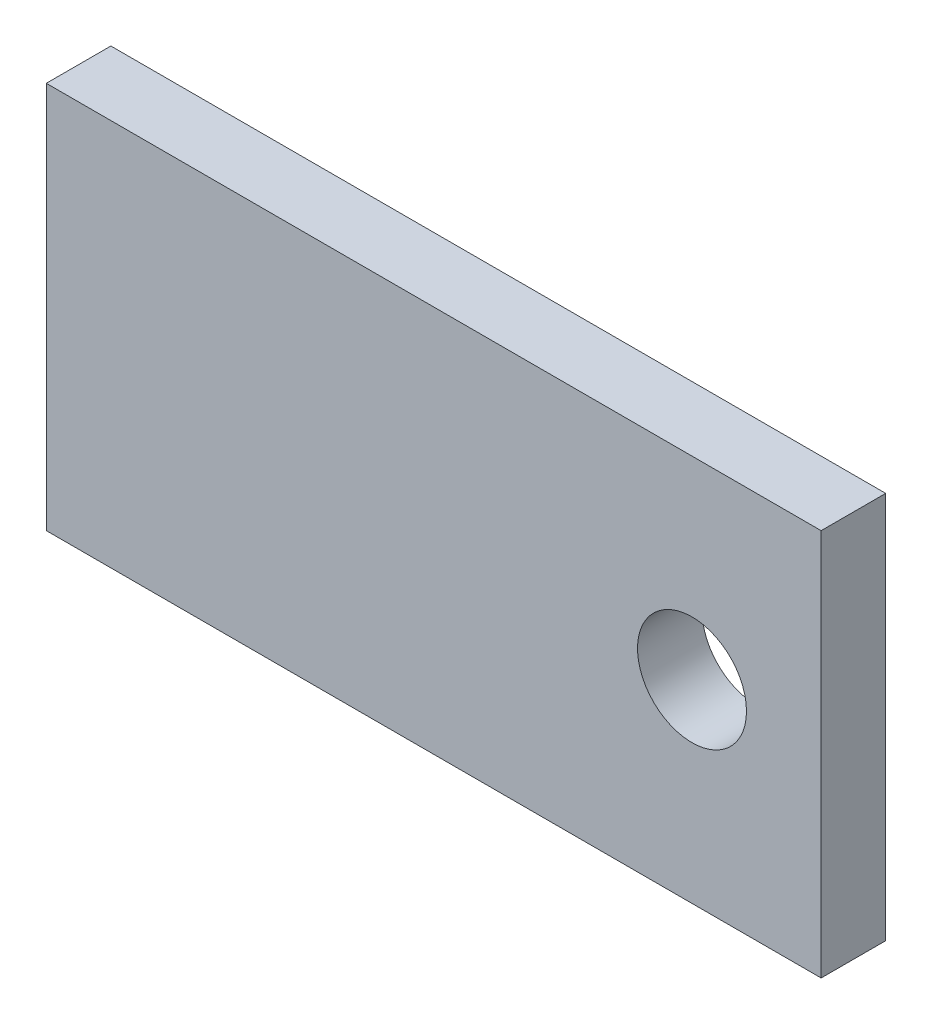
SolidWorks part; units mm, degrees
material "Plain Carbon Steel"
ref_plane "Front Plane" through (0, 0, 0) normal (0, 0, 1) x (1, 0, 0)
ref_plane "Top Plane" through (0, 0, 0) normal (0, 1, 0) x (1, 0, 0)
ref_plane "Right Plane" through (0, 0, 0) normal (1, 0, 0) x (0, 0, -1)
sketch "Sketch1" plane through (0, 0, 0) normal (0, 0, 1) x (1, 0, 0)
  line L1 (-38.1, -19.05) -> (38.1, -19.05)
  line L2 (-38.1, -19.05) -> (-38.1, 19.05)
  line L3 (-38.1, 19.05) -> (38.1, 19.05)
  line L4 (38.1, -19.05) -> (38.1, 19.05)
  line L5 (-38.1, -19.05) -> (38.1, 19.05) construction
  line L6 (-38.1, 19.05) -> (38.1, -19.05) construction
  point P0 (0, 0)
  dimension "D1" = 76.2
  dimension "D2" = 38.1
extrude "Extrude1" add sketch "Sketch1" along normal mid plane 6.35
sketch "Sketch2" plane through (0, 0, 3.175) normal (0, 0, 1) x (1, 0, 0)
  line L0 (38.1, 0) -> (25.4, 0) construction
  line L1 (38.1, -19.05) -> (38.1, 19.05) construction
  dimension "D1" = 12.7
hole_wizard "27/64 (0.42188) Diameter Hole1" positions "3DSketch1" profile "Sketch4" hole size "27/64" standard "Ansi Inch" end condition through all
sketch3d "3DSketch1"
  point P0 (25.4, 0, 3.175)
sketch "Sketch4" plane through (25.4, 0, 3.175) normal (1, 0, 0) x (0, -1, 0)
  line L0 (0, 0) -> (0, 6.35)
  line L1 (0, 6.35) -> (5.3579, 6.35)
  line L2 (5.3579, 6.35) -> (5.3579, 0)
  line L5 (5.3579, 0) -> (0, 0)
  line L11 (0, -6.35) -> (0, 107.95) construction
  dimension "Thru Hole Dia." = 10.7158
  dimension "Thru Hole Depth" = 6.35
sketch "Sketch5" plane through (0, 0, 0) normal (0, 0, 1) x (1, 0, 0)
  point P0 (25.4, 0)
